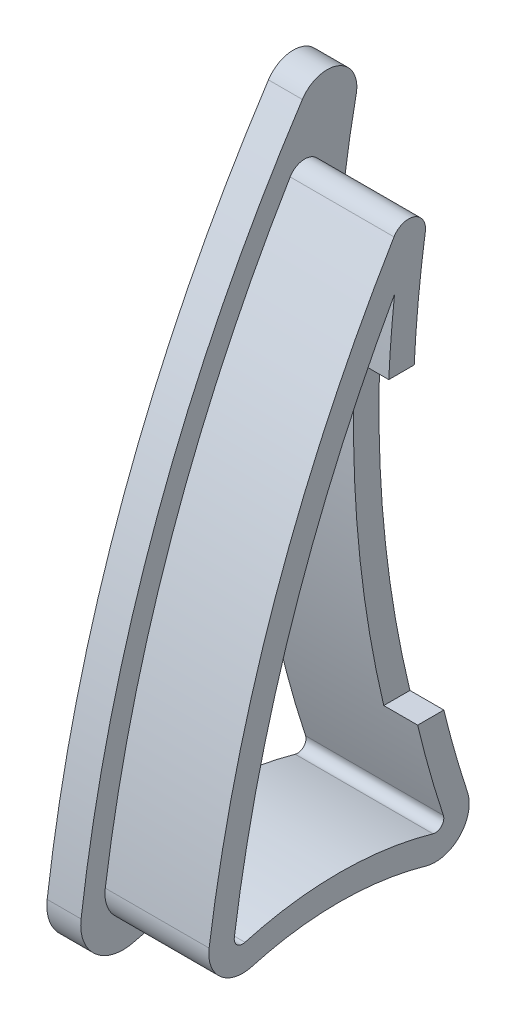
SolidWorks part; units mm, degrees
ref_plane "Front Plane" through (0, 0, 0) normal (0, 0, 1) x (1, 0, 0)
ref_plane "Top Plane" through (0, 0, 0) normal (0, 1, 0) x (1, 0, 0)
ref_plane "Right Plane" through (0, 0, 0) normal (1, 0, 0) x (0, 0, -1)
sketch "Sketch1" plane through (0, 0, 0) normal (0, 0, 1) x (1, 0, 0)
  line L0 (0, 0) -> (0, -27.8746) construction
  line L1 (-15.5575, 76.2) -> (15.5575, 76.2)
  line L2 (-15.5575, 76.2) -> (-15.5575, -76.2)
  line L3 (-15.5575, -76.2) -> (-7.8455, -76.2)
  line L4 (15.5575, 76.2) -> (15.5575, -76.2)
  line L5 (-15.5575, 76.2) -> (15.5575, -76.2) construction
  line L6 (-15.5575, -76.2) -> (15.5575, 76.2) construction
  line L7 (7.8455, -76.2) -> (9.525, -85.725)
  line L8 (-7.8455, -76.2) -> (-9.525, -85.725)
  line L9 (-9.525, -85.725) -> (9.525, -85.725)
  line L10 (7.8455, -76.2) -> (15.5575, -76.2)
  point P0 (0, 0)
  point P12 (0, -85.725)
  dimension "D1" = 31.115
  dimension "D2" = 152.4
  dimension "D3" = 20
  dimension "D4" = 19.05
  dimension "D5" = 9.525
extrude "Boss-Extrude1" add sketch "Sketch1" along normal blind 76.2
sketch "Sketch2" plane through (15.5575, 0, 0) normal (1, 0, 0) x (0, 0, -1)
  line L0 (-76.2, -76.2) -> (0, -76.2) construction
  line L1 (0, -85.725) -> (-6.985, -85.725)
  line L2 (0, -85.725) -> (0, -76.2)
  line L3 (0, -76.2) -> (-6.985, -76.2)
  line L4 (-6.985, -85.725) -> (-6.985, -76.2)
  dimension "D1" = 6.985
extrude "Cut-Extrude1" cut sketch "Sketch2" against normal through all
sketch "Sketch3" plane through (15.5575, 0, 0) normal (1, 0, 0) x (0, 0, -1)
  line L14 (-76.2, 76.2) -> (0, 76.2) construction
  line L15 (-76.2, -76.2) -> (-76.2, 76.2) construction
  line L16 (-76.2, -85.725) -> (-76.2, -76.2) construction
  line L17 (0, -76.2) -> (0, 76.2) construction
  line L18 (-76.2, -85.725) -> (-76.2, -76.2)
  line L19 (-76.2, -76.2) -> (-76.2, 76.2)
  line L20 (-76.2, 76.2) -> (-6.5418, 76.2)
  line L21 (0, -76.2) -> (0, 67.7594)
  arc A4 (-6.5418, 76.2) -> (-76.2, -85.725) centre (146.8317, -85.725) ccw
  arc A5 (0, 67.7594) -> (0, -76.2) centre (133.1876, -4.2203) ccw
  point P3 (0, 67.7594)
extrude "Cut-Extrude2" cut sketch "Sketch3" against normal through all
sketch "Sketch6" plane through (15.5575, 0, 0) normal (1, 0, 0) x (0, 0, -1)
  line L6 (-62.3225, -63.5) -> (-19.8242, -63.5)
  arc A2 (-28.9344, -61.8834) -> (-22.7163, -55.413) centre (-27.5427, -56.9978) ccw
  arc A3 (-55.008, -61.8834) -> (-61.4297, -56.2868) centre (-56.3997, -56.9978) cw
  arc A6 (-26.5466, 33.3523) -> (-19.8242, -63.5) centre (133.1876, -4.2203) ccw
  arc A7 (-26.5466, 33.3523) -> (-62.3225, -63.5) centre (146.8317, -85.725) ccw
  arc A11 (-26.5466, 33.3523) -> (-22.7163, -55.413) centre (133.1876, -4.2203) ccw
  arc A12 (-26.5466, 33.3523) -> (-61.4297, -56.2868) centre (146.8317, -85.725) ccw
  arc A13 (-55.008, -61.8834) -> (-28.9344, -61.8834) centre (-41.9712, -107.6502) cw
  point P7 (0, 0)
  dimension "D2" = 5.08
  dimension "D1" = 12.7
extrude "Cut-Extrude3" cut sketch "Sketch6" against normal through all
fillet "Fillet1" radius 2.54 1 edges at (0, 33.3523, 26.5466)
sketch "Sketch7" plane through (0, 0, 0) normal (1, 0, 0) x (0, 0, -1)
  line L0 (-30.6991, 4.0162) -> (-17.9818, 4.0162)
  line L2 (-26.2642, -42.9738) -> (-13.1619, -42.9738)
  arc A0 (-29.0387, 20.4641) -> (-22.7163, -55.413) centre (133.1876, -4.2203) ccw construction
  arc A1 (0, 67.7594) -> (0, -76.2) centre (133.1876, -4.2203) ccw construction
  arc A2 (-30.6991, 4.0162) -> (-26.2642, -42.9738) centre (133.1876, -4.2203) ccw
  arc A3 (-17.9818, 4.0162) -> (-13.1619, -42.9738) centre (133.1876, -4.2203) ccw
  dimension "D1" = 46.99
extrude "Cut-Extrude4" cut sketch "Sketch7" against normal mid plane 10.16
sketch "Sketch9" plane through (15.5575, 0, 0) normal (1, 0, 0) x (0, 0, -1)
  line L0 (-6.5418, 76.2) -> (0, 67.7594)
ref_plane "Plane2" through (15.5575, 76.2, 6.5418) normal (0, -0.7904, -0.6126) x (-1, 0, 0)
sketch "Sketch10" plane through (15.5575, 76.2, 6.5418) normal (0, -0.7904, -0.6126) x (-1, 0, 0)
  line L4 (15.5575, 5.1706) -> (15.5575, 19.0294) construction
  line L5 (0, 5.1706) -> (31.115, 5.1706) construction
  line L6 (0, 5.1706) -> (6.985, 5.1706)
  line L7 (6.985, 5.1706) -> (0, -3.6559)
  line L8 (0, 0) -> (0, -88.1882) construction
  line L9 (0, 5.1706) -> (0, -3.6559)
  line L10 (31.115, 5.1706) -> (31.115, -3.6559)
  line L11 (24.13, 5.1706) -> (31.115, -3.6559)
  line L12 (31.115, 5.1706) -> (24.13, 5.1706)
  dimension "D1" = 8.8265
  dimension "D2" = 6.985
extrude "Cut-Extrude6" cut sketch "Sketch10" against normal mid plane 30.226
fillet "Fillet2" radius 0.508 5 edges at (-15.5575, 5.0909, 56.873) (-14.1116, 74.9302, 7.8714) (0, 76.2, 6.5418) (15.5575, 5.0909, 56.873) (14.1116, 74.9302, 7.8714)
sketch "Sketch11" plane through (15.5575, 0, 0) normal (1, 0, 0) x (0, 0, -1)
  arc A0 (-61.4297, -56.2868) -> (-55.008, -61.8834) centre (-56.3997, -56.9978) ccw construction
  arc A1 (-28.9344, -61.8834) -> (-55.008, -61.8834) centre (-41.9712, -107.6502) ccw construction
  arc A2 (-28.9344, -61.8834) -> (-22.7163, -55.413) centre (-27.5427, -56.9978) ccw construction
  arc A3 (-29.0387, 20.4641) -> (-22.7163, -55.413) centre (133.1876, -4.2203) ccw construction
  arc A4 (-33.7303, 22.1489) -> (-61.4297, -56.2868) centre (146.8317, -85.725) ccw construction
  arc A5 (-29.0387, 20.4641) -> (-33.7303, 22.1489) centre (-31.5498, 20.8462) ccw construction
  arc A6 (-61.4297, -56.2868) -> (-55.008, -61.8834) centre (-56.3997, -56.9978) ccw
  arc A7 (-28.9344, -61.8834) -> (-55.008, -61.8834) centre (-41.9712, -107.6502) ccw
  arc A8 (-28.9344, -61.8834) -> (-22.7163, -55.413) centre (-27.5427, -56.9978) ccw
  arc A9 (-29.0387, 20.4641) -> (-22.7163, -55.413) centre (133.1876, -4.2203) ccw
  arc A10 (-33.7303, 22.1489) -> (-61.4297, -56.2868) centre (146.8317, -85.725) ccw
  arc A11 (-29.0387, 20.4641) -> (-33.7303, 22.1489) centre (-31.5498, 20.8462) ccw
  arc A12 (-57.6572, -56.82) -> (-56.0518, -58.2192) centre (-56.3997, -56.9978) ccw
  arc A13 (-27.8906, -58.2192) -> (-56.0518, -58.2192) centre (-41.9712, -107.6502) ccw
  arc A14 (-27.8906, -58.2192) -> (-26.3361, -56.6016) centre (-27.5427, -56.9978) ccw
  arc A15 (-33.6511, 14.6602) -> (-26.3361, -56.6016) centre (133.1876, -4.2203) ccw
  arc A16 (-33.6511, 14.6602) -> (-33.6511, 14.6602) centre (-33.6511, 14.6602) ccw
  arc A17 (-33.6511, 14.6602) -> (-57.6572, -56.82) centre (146.8317, -85.725) ccw
  dimension "D1" = 3.81
extrude "Boss-Extrude2" add sketch "Sketch11" against normal blind 15.5575 separate body
sketch "Sketch12" plane through (15.5575, 0, 0) normal (1, 0, 0) x (0, 0, -1)
  line L4 (-66.0068, -67.31) -> (-14.1573, -67.31)
  arc A0 (-23.8317, 27.9628) -> (-31.9051, 31.29) centre (-28.1862, 28.8553) ccw
  arc A1 (-57.0833, -65.4052) -> (-25.7615, -65.4052) centre (-41.4224, -122.6783) cw
  arc A2 (-27.8906, -58.2192) -> (-26.3361, -56.6016) centre (-27.5427, -56.9978) ccw construction
  arc A3 (-25.7615, -65.4052) -> (-18.0933, -57.1818) centre (-24.0866, -59.28) ccw
  arc A4 (-65.0563, -58.4699) -> (-57.0833, -65.4052) centre (-58.7582, -59.28) ccw
  arc A5 (-27.8906, -58.2192) -> (-56.0518, -58.2192) centre (-41.9712, -107.6502) ccw construction
  arc A6 (-17.255, 51.0774) -> (-66.0068, -67.31) centre (146.8317, -85.725) ccw
  arc A7 (-17.255, 51.0774) -> (-14.1573, -67.31) centre (133.1876, -4.2203) ccw
  arc A8 (-31.9051, 31.29) -> (-65.0563, -58.4699) centre (146.8317, -85.725) ccw
  arc A9 (-23.8317, 27.9628) -> (-18.0933, -57.1818) centre (133.1876, -4.2203) ccw
  arc A10 (-57.6572, -56.82) -> (-56.0518, -58.2192) centre (-56.3997, -56.9978) ccw construction
  arc A11 (-33.6511, 14.6602) -> (-57.6572, -56.82) centre (146.8317, -85.725) ccw construction
  arc A12 (-33.6511, 14.6602) -> (-26.3361, -56.6016) centre (133.1876, -4.2203) ccw construction
  arc A13 (-27.8906, -58.2192) -> (-26.3361, -56.6016) centre (-27.5427, -56.9978) ccw
  arc A14 (-27.8906, -58.2192) -> (-56.0518, -58.2192) centre (-41.9712, -107.6502) ccw
  arc A15 (-57.6572, -56.82) -> (-56.0518, -58.2192) centre (-56.3997, -56.9978) ccw
  arc A16 (-33.6511, 14.6602) -> (-57.6572, -56.82) centre (146.8317, -85.725) ccw
  arc A17 (-33.6511, 14.6602) -> (-26.3361, -56.6016) centre (133.1876, -4.2203) ccw
  point P11 (0, 0)
  dimension "D2" = 6.35
  dimension "D3" = 4.445
  dimension "D1" = 8.89
extrude "Boss-Extrude3" add sketch "Sketch12" along normal blind 5.08 separate body
sketch "Sketch13" plane through (0, 0, 0) normal (1, 0, 0) x (0, 0, -1)
  line L0 (-17.9818, 4.0162) -> (-34.5138, 4.0162)
  line L1 (-13.1619, -42.9738) -> (-30.1825, -42.9738)
  arc A0 (-33.6511, 14.6602) -> (-26.3361, -56.6016) centre (133.1876, -4.2203) ccw construction
  arc A1 (-1.8645, 64.1972) -> (0, -76.2) centre (133.1876, -4.2203) ccw construction
  arc A2 (-17.9818, 4.0162) -> (-13.1619, -42.9738) centre (133.1876, -4.2203) ccw
  arc A3 (-34.5138, 4.0162) -> (-30.1825, -42.9738) centre (133.1876, -4.2203) ccw
extrude "Cut-Extrude7" cut sketch "Sketch13" against normal mid plane 10.16
delete or keep bodies "Body-Delete/Keep 1" type delete bodies bodies 107
combine bodies "Combine1" operation type add bodies to combine 115 114
mirror "Mirror1" about plane through (0, -71.3614, -45.216) normal (1, 0, 0) of bodies 116
delete or keep bodies "Body-Delete/Keep 2" type delete bodies bodies 116
